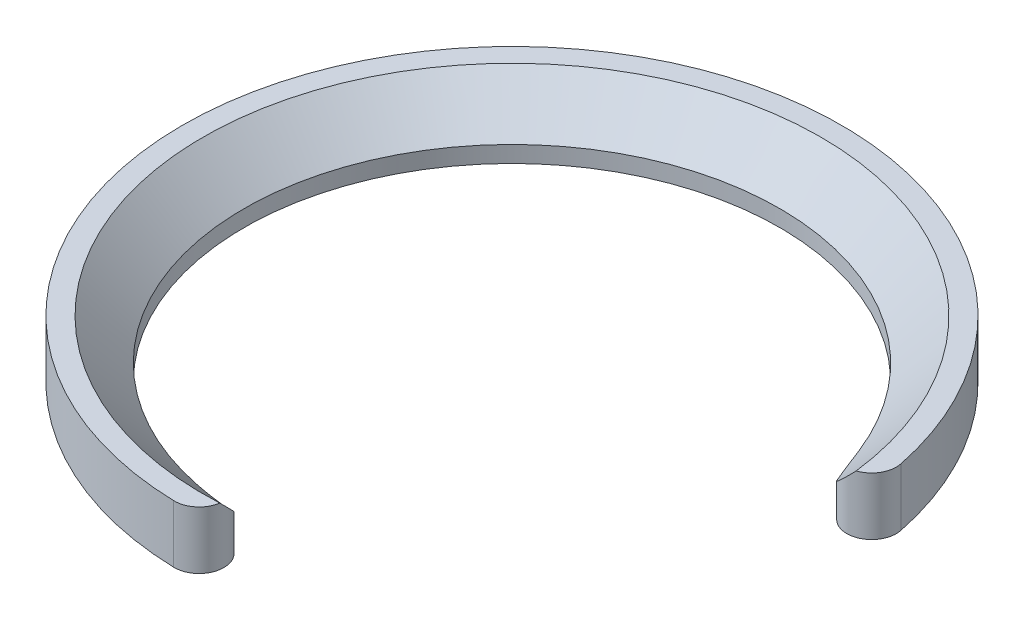
SolidWorks part; units mm, degrees
ref_plane "Front Plane" through (0, 0, 0) normal (0, 0, 1) x (1, 0, 0)
ref_plane "Top Plane" through (0, 0, 0) normal (0, 1, 0) x (1, 0, 0)
ref_plane "Right Plane" through (0, 0, 0) normal (1, 0, 0) x (0, 0, -1)
sketch "Sketch1" plane through (0, 0, 0) normal (0, 0, 1) x (1, 0, 0)
  line L0 (13, 0) -> (13, 0.8)
  line L1 (13, 0.8) -> (15, 2.8)
  line L2 (15, 2.8) -> (16, 2.8)
  line L3 (16, 2.8) -> (16, 0)
  line L4 (16, 0) -> (13, 0)
  line L5 (13, 0) -> (0, 0) construction
  line L6 (0, 0) -> (0, 2.8) construction
  dimension "D1" = 2.8
  dimension "D2" = 45
  dimension "D3" = 0.8
  dimension "D4" = 3
  dimension "D5" = 13
revolve "Revolve1" add sketch "Sketch1" angle 280 about L6
fillet "Fillet1" radius 10 2 edges at (13, 0.4, 0) (2.2574, 0.4, 12.8025)
fillet "Fillet2" radius 1.2 2 edges at (16, 1.4, 0) (2.7784, 1.4, 15.7569)
